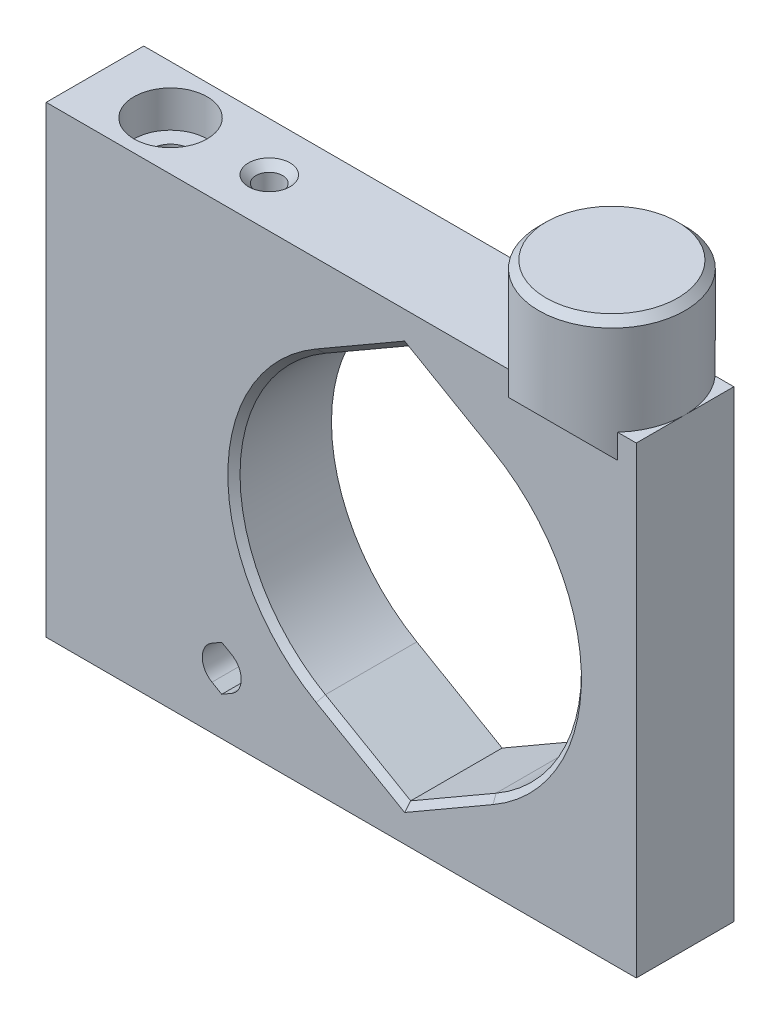
SolidWorks part; units mm, degrees
ref_plane "Front Plane" through (0, 0, 0) normal (0, 0, 1) x (1, 0, 0)
ref_plane "Top Plane" through (0, 0, 0) normal (0, 1, 0) x (1, 0, 0)
ref_plane "Right Plane" through (0, 0, 0) normal (1, 0, 0) x (0, 0, -1)
sketch "Sketch1" plane through (0, 0, 0) normal (0, 0, 1) x (1, 0, 0)
  line L0 (-7, 12.1244) -> (0, 16.1658)
  line L1 (0, 16.1658) -> (7, 12.1244)
  line L2 (-7, -12.1244) -> (0, -16.1658)
  line L3 (0, -16.1658) -> (7, -12.1244)
  line L4 (-26.2, 19) -> (-26.2, 16) construction
  line L5 (19, 19) -> (-29.4, 19)
  line L6 (19, 19) -> (19, -19)
  line L7 (19, -19) -> (-29.4, -19)
  line L8 (-29.4, 19) -> (-29.4, -19)
  line L9 (-26.2, 16) -> (-24.8, 16) construction
  line L10 (-24.8, 16) -> (-24.8, -16) construction
  line L11 (-24.8, -16) -> (-25.95, -16) construction
  line L12 (-25.95, -16) -> (-25.95, -19) construction
  line L13 (-20.45, -19) -> (-20.45, -16) construction
  line L14 (-20.45, -16) -> (-21.6, -16) construction
  line L15 (-21.6, -16) -> (-21.6, 16) construction
  line L16 (-21.6, 16) -> (-20.2, 16) construction
  line L17 (-20.2, 16) -> (-20.2, 19) construction
  line L18 (-15.8, -12.6144) -> (-15, -12.1525)
  line L19 (-17.75, -12.4123) -> (-17.75, -15.5877) construction
  line L20 (-17.75, -15.5877) -> (-15, -17.1754) construction
  line L21 (-15, -17.1754) -> (-12.25, -15.5877) construction
  line L22 (-12.25, -15.5877) -> (-12.25, -12.4123) construction
  line L23 (-12.25, -12.4123) -> (-15, -10.8246) construction
  line L24 (-15, -10.8246) -> (-17.75, -12.4123) construction
  line L25 (-15, -12.1525) -> (-14.2, -12.6144)
  line L26 (-15.8, -15.3856) -> (-15, -15.8475)
  line L27 (-15, -15.8475) -> (-14.2, -15.3856)
  line L28 (-16.2, 19) -> (-16.2, 14) construction
  line L29 (-16.2, 14) -> (-14, 14) construction
  line L30 (-14, 14) -> (-14, 19) construction
  arc A0 (-7, 12.1244) -> (-7, -12.1244) centre (0, 0) ccw
  arc A1 (7, -12.1244) -> (7, 12.1244) centre (0, 0) ccw
  circle A2 centre (0, 0) radius 19 construction
  arc A3 (-15.8, -12.6144) -> (-15.8, -15.3856) centre (-15, -14) ccw
  circle A4 centre (-15, -14) radius 2.75 construction
  arc A5 (-14.2, -15.3856) -> (-14.2, -12.6144) centre (-15, -14) ccw
  point P27 (-14.0978, 14)
  point P42 (0, 0)
  point P45 (0, 0)
  point P46 (0, 0)
  point P47 (0, 0)
  dimension "D2" = 14
  dimension "D3" = 5
  dimension "D11" = 120
  dimension "D14" = 1.6
  dimension "D1" = 120
  dimension "D4" = 5.5
  dimension "D5" = 3.2
  dimension "D6" = 6
  dimension "D7" = 3
  dimension "D8" = 3
  dimension "D9" = 3.2
  dimension "D10" = 5.5
  dimension "D12" = 5
  dimension "D13" = 15
  dimension "D15" = 5
  dimension "D16" = 2.2
  dimension "D17" = 4
  dimension "D18" = 14
extrude "Boss-Extrude1" add sketch "Sketch1" along normal blind 8
sketch "Sketch2" plane through (0, 19, 0) normal (0, 1, 0) x (1, 0, 0)
  line L0 (-26.2, 0) -> (-26.2, -8) construction
  line L1 (19, -8) -> (-29.4, -8) construction
  line L2 (-20.2, 0) -> (-20.2, -8) construction
  line L3 (-26.2, -4) -> (-20.2, -4) construction
  circle A0 centre (-23.2, -4) radius 3
extrude "Cut-Extrude1" cut sketch "Sketch2" against normal up to vertex (3 mm away) up to point (-20.2, 16, 0)
sketch "Sketch3" plane through (0, 16, 0) normal (0, 1, 0) x (1, 0, 0)
  line L0 (-24.8, 0) -> (-24.8, -8) construction
  line L1 (-21.6, 0) -> (-21.6, -8) construction
  line L2 (19, -8) -> (-29.4, -8) construction
  line L3 (-24.8, -4) -> (-21.6, -4) construction
  circle A0 centre (-23.2, -4) radius 1.6
extrude "Cut-Extrude2" cut sketch "Sketch3" against normal up to vertex (32 mm away) up to point (-21.6, -16, 0)
sketch "Sketch4" plane through (0, -19, 0) normal (0, -1, 0) x (1, 0, 0)
  line L0 (-25.95, 0) -> (-25.95, 8) construction
  line L1 (-29.4, 8) -> (19, 8) construction
  line L2 (-20.45, 0) -> (-20.45, 8) construction
  line L3 (-25.95, 4) -> (-20.45, 4) construction
  line L5 (-25.95, 5.5877) -> (-25.95, 2.4123)
  line L6 (-25.95, 2.4123) -> (-23.2, 0.8246)
  line L7 (-23.2, 0.8246) -> (-20.45, 2.4123)
  line L8 (-20.45, 2.4123) -> (-20.45, 5.5877)
  line L9 (-20.45, 5.5877) -> (-23.2, 7.1754)
  line L10 (-23.2, 7.1754) -> (-25.95, 5.5877)
  circle A0 centre (-23.2, 4) radius 2.75 construction
  point P11 (0, 0)
  point P19 (0, 0)
extrude "Cut-Extrude3" cut sketch "Sketch4" against normal up to vertex (3 mm away) up to point (-21.6, -16, 0)
sketch "Sketch5" plane through (0, 0, 0) normal (0, 0, -1) x (-1, 0, 0)
  line L0 (12.25, -15.5877) -> (12.25, -12.4123) construction
  line L1 (12.25, -12.4123) -> (15, -10.8246) construction
  line L2 (15, -10.8246) -> (17.75, -12.4123) construction
  line L3 (17.75, -12.4123) -> (17.75, -15.5877) construction
  line L4 (17.75, -15.5877) -> (15, -17.1754) construction
  line L5 (15, -17.1754) -> (12.25, -15.5877) construction
  line L6 (12.25, -15.5877) -> (12.25, -12.4123)
  line L7 (12.25, -12.4123) -> (15, -10.8246)
  line L8 (15, -10.8246) -> (17.75, -12.4123)
  line L9 (17.75, -12.4123) -> (17.75, -15.5877)
  line L10 (17.75, -15.5877) -> (15, -17.1754)
  line L11 (15, -17.1754) -> (12.25, -15.5877)
extrude "Cut-Extrude4" cut sketch "Sketch5" against normal blind 3
sketch "Sketch6" plane through (0, 19, 0) normal (0, 1, 0) x (1, 0, 0)
  line L0 (-16.2, 0) -> (-16.2, -8) construction
  line L1 (19, -8) -> (-29.4, -8) construction
  line L2 (-14, 0) -> (-14, -8) construction
  line L3 (-16.2, -4) -> (-14, -4) construction
  circle A0 centre (-15.1, -4) radius 1.1
extrude "Cut-Extrude5" cut sketch "Sketch6" against normal up to vertex (5 mm away) up to point (-16.2, 14, 0)
chamfer "Chamfer1" distance 0.6 angle 45 7 edges at (-21.825, -19, 1.6184) (-20.45, -19, 4) (-21.825, -19, 6.3816) (-24.575, -19, 6.3816) (-25.95, -19, 4) (-24.575, -19, 1.6184) (-15.1, 19, 5.1)
chamfer "Chamfer2" distance 0.5 angle 45 6 edges at (3.5, -14.1451, 8) (14, 0, 8) (3.5, 14.1451, 8) (-3.5, 14.1451, 8) (-3.5, -14.1451, 8) (-14, 0, 8)
chamfer "Chamfer3" distance 1.6 angle 45 1 edges at (-23.2, -16, 5.6)
sketch "Sketch8" plane through (0, 19, 0) normal (0, 1, 0) x (1, 0, 0)
  line L0 (19, -8) -> (19, 0) construction
  line L1 (13, -4) -> (19, -4) construction
  circle A0 centre (13, -4) radius 6
  point P2 (0, 0)
  dimension "D1" = 12
extrude "Boss-Extrude2" add sketch "Sketch8" along normal blind 8
chamfer "Chamfer4" distance 2 angle 45 2 edges at (13, 19, 0) (13, 19, 8)
chamfer "Chamfer5" distance 0.6 angle 45 1 edges at (13, 27, 10)
